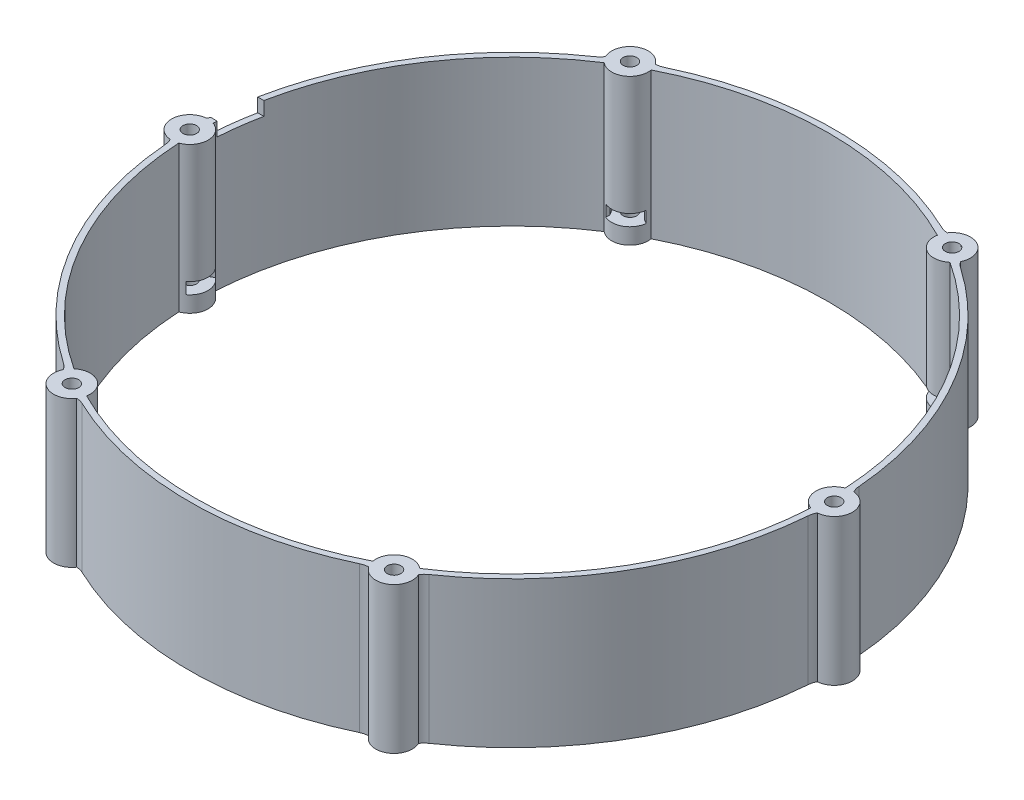
SolidWorks part; units mm, degrees
ref_plane "前视基准面" through (0, 0, 0) normal (0, 0, 1) x (1, 0, 0)
ref_plane "上视基准面" through (0, 0, 0) normal (0, 1, 0) x (1, 0, 0)
ref_plane "右视基准面" through (0, 0, 0) normal (1, 0, 0) x (0, 0, -1)
sketch "草图1" plane through (0, 0, 0) normal (0, 1, 0) x (1, 0, 0)
  line L12 (-35.25, -61.0548) -> (0, 0) construction
  line L13 (-67.3629, 4.3002) -> (-9.579, 4.3002)
  line L14 (-67.3629, -4.3002) -> (-9.579, -4.3002)
  line L15 (9.579, 4.3002) -> (67.3629, 4.3002)
  line L16 (9.579, -4.3002) -> (67.3629, -4.3002)
  line L17 (1.0654, -10.4458) -> (29.9573, -60.4881)
  line L18 (8.5136, -6.1456) -> (37.4056, -56.1878)
  line L19 (-29.9573, 60.4881) -> (-1.0654, 10.4458)
  line L20 (-37.4056, 56.1878) -> (-8.5136, 6.1456)
  line L21 (-8.5136, -6.1456) -> (-37.4056, -56.1878)
  line L22 (-1.0654, -10.4458) -> (-29.9573, -60.4881)
  line L23 (37.4056, 56.1878) -> (8.5136, 6.1456)
  line L24 (29.9573, 60.4881) -> (1.0654, 10.4458)
  line L25 (-9.579, 4.3002) -> (-67.3629, 4.3002)
  line L26 (-9.579, -4.3002) -> (-67.3629, -4.3002)
  line L27 (67.3629, -4.3002) -> (9.579, -4.3002)
  line L28 (67.3629, 4.3002) -> (9.579, 4.3002)
  line L29 (-1.0654, 10.4458) -> (-29.9573, 60.4881)
  line L30 (-8.5136, 6.1456) -> (-37.4056, 56.1878)
  line L31 (29.9573, -60.4881) -> (1.0654, -10.4458)
  line L32 (37.4056, -56.1878) -> (8.5136, -6.1456)
  line L33 (8.5136, 6.1456) -> (37.4056, 56.1878)
  line L34 (1.0654, 10.4458) -> (29.9573, 60.4881)
  line L35 (-37.4056, -56.1878) -> (-8.5136, -6.1456)
  line L36 (-29.9573, -60.4881) -> (-1.0654, -10.4458)
  line L37 (10.5, 0) -> (70.5, 0) construction
  line L38 (-10.5, 0) -> (9.5, 0) construction
  line L47 (-31.5, -54.5596) -> (-6.5, -11.2583) construction
  line L48 (-32.799, -53.8096) -> (-7.799, -10.5083)
  line L49 (-30.201, -55.3096) -> (-5.201, -12.0083)
  line L50 (-63, 0) -> (-13, 0) construction
  line L51 (-63, 1.5) -> (-13, 1.5)
  line L52 (-63, -1.5) -> (-13, -1.5)
  line L53 (-31.5, 54.5596) -> (-6.5, 11.2583) construction
  line L54 (-30.201, 55.3096) -> (-5.201, 12.0083)
  line L55 (-32.799, 53.8096) -> (-7.799, 10.5083)
  line L56 (31.5, 54.5596) -> (6.5, 11.2583) construction
  line L57 (32.799, 53.8096) -> (7.799, 10.5083)
  line L58 (30.201, 55.3096) -> (5.201, 12.0083)
  line L59 (63, 0) -> (13, 0) construction
  line L60 (63, -1.5) -> (13, -1.5)
  line L61 (63, 1.5) -> (13, 1.5)
  line L62 (31.5, -54.5596) -> (6.5, -11.2583) construction
  line L63 (30.201, -55.3096) -> (5.201, -12.0083)
  line L64 (32.799, -53.8096) -> (7.799, -10.5083)
  arc A0 (-7.8594, 1.4934) -> (-7.8594, -1.4934) centre (0, 0) ccw construction
  circle A1 centre (-8, 0) radius 1.5
  circle A2 centre (0, 8) radius 1.5
  circle A3 centre (8, 0) radius 1.5
  circle A4 centre (0, -8) radius 1.5
  arc A5 (-8.5136, 6.1456) -> (-9.579, 4.3002) centre (0, 0) ccw
  arc A6 (-67.3629, -4.3002) -> (-37.4056, -56.1878) centre (0, 0) ccw
  arc A7 (-70.5, 3) -> (-70.5, -3) centre (-70.5, 0) ccw
  circle A8 centre (-70.5, 0) radius 1.5
  arc A9 (-32.6519, 62.5548) -> (-37.8481, 59.5548) centre (-35.25, 61.0548) ccw
  circle A10 centre (-35.25, 61.0548) radius 1.5
  arc A11 (37.8481, 59.5548) -> (32.6519, 62.5548) centre (35.25, 61.0548) ccw
  circle A12 centre (35.25, 61.0548) radius 1.5
  arc A13 (70.5, -3) -> (70.5, 3) centre (70.5, 0) ccw
  circle A14 centre (70.5, 0) radius 1.5
  arc A15 (32.6519, -62.5548) -> (37.8481, -59.5548) centre (35.25, -61.0548) ccw
  circle A16 centre (35.25, -61.0548) radius 1.5
  arc A17 (-37.8481, -59.5548) -> (-32.6519, -62.5548) centre (-35.25, -61.0548) ccw
  circle A18 centre (-35.25, -61.0548) radius 1.5
  arc A21 (1.4934, 7.8594) -> (-6.746, 4.3002) centre (0, 0) ccw construction
  arc A22 (-1.4934, -7.8594) -> (1.4934, -7.8594) centre (0, 0) ccw construction
  arc A23 (7.8594, -1.4934) -> (6.746, 4.3002) centre (0, 0) ccw construction
  circle A24 centre (0, 0) radius 4.5
  arc A25 (1.0654, 10.4458) -> (-1.0654, 10.4458) centre (0, 0) ccw
  arc A26 (9.579, 4.3002) -> (8.5136, 6.1456) centre (0, 0) ccw
  arc A27 (8.5136, -6.1456) -> (9.579, -4.3002) centre (0, 0) ccw
  arc A28 (-1.0654, -10.4458) -> (1.0654, -10.4458) centre (0, 0) ccw
  arc A29 (-9.579, -4.3002) -> (-8.5136, -6.1456) centre (0, 0) ccw
  arc A30 (-37.4056, 56.1878) -> (-67.3629, 4.3002) centre (0, 0) ccw
  arc A31 (29.9573, 60.4881) -> (-29.9573, 60.4881) centre (0, 0) ccw
  arc A32 (67.3629, 4.3002) -> (37.4056, 56.1878) centre (0, 0) ccw
  arc A33 (37.4056, -56.1878) -> (67.3629, -4.3002) centre (0, 0) ccw
  arc A34 (-29.9573, -60.4881) -> (29.9573, -60.4881) centre (0, 0) ccw
  arc A35 (32.6519, 62.5548) -> (-32.6519, 62.5548) centre (0, 0) ccw
  arc A36 (70.5, 3) -> (37.8481, 59.5548) centre (0, 0) ccw
  arc A37 (37.8481, -59.5548) -> (70.5, -3) centre (0, 0) ccw
  arc A38 (-32.6519, -62.5548) -> (32.6519, -62.5548) centre (0, 0) ccw
  arc A39 (-70.5, -3) -> (-37.8481, -59.5548) centre (0, 0) ccw
  arc A40 (-37.8481, 59.5548) -> (-70.5, 3) centre (0, 0) ccw
  arc A41 (-32.799, -53.8096) -> (-30.201, -55.3096) centre (-31.5, -54.5596) ccw
  arc A42 (-5.201, -12.0083) -> (-7.799, -10.5083) centre (-6.5, -11.2583) ccw
  arc A43 (-63, 1.5) -> (-63, -1.5) centre (-63, 0) ccw
  arc A44 (-13, -1.5) -> (-13, 1.5) centre (-13, 0) ccw
  arc A45 (-30.201, 55.3096) -> (-32.799, 53.8096) centre (-31.5, 54.5596) ccw
  arc A46 (-7.799, 10.5083) -> (-5.201, 12.0083) centre (-6.5, 11.2583) ccw
  arc A47 (32.799, 53.8096) -> (30.201, 55.3096) centre (31.5, 54.5596) ccw
  arc A48 (5.201, 12.0083) -> (7.799, 10.5083) centre (6.5, 11.2583) ccw
  arc A49 (63, -1.5) -> (63, 1.5) centre (63, 0) ccw
  arc A50 (13, 1.5) -> (13, -1.5) centre (13, 0) ccw
  arc A51 (30.201, -55.3096) -> (32.799, -53.8096) centre (31.5, -54.5596) ccw
  arc A52 (7.799, -10.5083) -> (5.201, -12.0083) centre (6.5, -11.2583) ccw
  point P14 (0, 0)
  point P15 (0, 0)
  point P20 (-19, -32.909)
  point P51 (-38, 0)
  point P52 (0, 0)
  point P92 (-19, 32.909)
  point P99 (19, 32.909)
  point P106 (38, 0)
  point P111 (0, 0)
  point P130 (19, -32.909)
  point P135 (0, 0)
  dimension "D1" = 16
  dimension "D2" = 3
  dimension "D4" = 2.5
  dimension "D5" = 135
  dimension "D6" = 6
  dimension "D7" = 3
  dimension "D9" = 9
  dimension "D11" = 50
  dimension "D8" = 6
  dimension "D12" = 13
  dimension "D13" = 3
  dimension "D3" = 4
  dimension "D10" = 6
  dimension "D14" = 6
extrude "凸台-拉伸1" add sketch "草图1" along normal blind 4 contours A9 A40 A7 A39 A17 A38 A15 A37 A13 A36 A11 A35 A52 L64 A51 L63 A50 L61 A49 L60 A48 L58 A47 L57 A46 L55 A45 L54 A44 L52 A43 L51 A42 L49 A41 L48 L14 A29 L21 A6 A1 A2 region at (-59.3453, 0, -34.263)
fillet "圆角1" radius 4 24 edges at (-37.4056, 2, 56.1878) (-67.3629, 2, 4.3002) (-70.5, 2, 3) (-70.5, 2, -3) (-67.3629, 2, -4.3002) (-37.4056, 2, -56.1878) (-29.9573, 2, -60.4881) (-37.8481, 2, -59.5548) (-32.6519, 2, -62.5548) (32.6519, 2, -62.5548) (29.9573, 2, -60.4881) (37.4056, 2, -56.1878) (37.8481, 2, -59.5548) (70.5, 2, -3) (70.5, 2, 3) (67.3629, 2, -4.3002) (67.3629, 2, 4.3002) (37.8481, 2, 59.5548) (37.4056, 2, 56.1878) (32.6519, 2, 62.5548) (29.9573, 2, 60.4881) (-37.8481, 2, 59.5548) (-29.9573, 2, 60.4881) (-32.6519, 2, 62.5548)
fillet "圆角2" radius 4 12 edges at (-1.0654, 2, 10.4458) (-8.5136, 2, 6.1456) (-9.579, 2, 4.3002) (-9.579, 2, -4.3002) (-8.5136, 2, -6.1456) (1.0654, 2, -10.4458) (-1.0654, 2, -10.4458) (9.579, 2, -4.3002) (8.5136, 2, -6.1456) (9.579, 2, 4.3002) (8.5136, 2, 6.1456) (1.0654, 2, 10.4458)
sketch "草图2" plane through (0, 0, 0) normal (0, -1, 0) x (-1, 0, 0)
  line L0 (23.0864, -63.4293) -> (23.5994, -64.8388)
  line L1 (0, 0) -> (0, -46.6688) construction
  line L2 (-23.0864, -63.4293) -> (-23.5994, -64.8388)
  line L3 (-43.3882, -51.708) -> (-44.3523, -52.8571)
  line L4 (-66.4745, -11.7213) -> (-67.9517, -11.9817)
  line L5 (-66.4745, 11.7213) -> (-67.9517, 11.9817)
  line L6 (-43.3882, 51.708) -> (-44.3523, 52.8571)
  line L7 (-23.0864, 63.4293) -> (-23.5994, 64.8388)
  line L8 (23.0864, 63.4293) -> (23.5994, 64.8388)
  line L9 (43.3882, 51.708) -> (44.3523, 52.8571)
  line L10 (66.4745, 11.7213) -> (67.9517, 11.9817)
  line L11 (66.4745, -11.7213) -> (67.9517, -11.9817)
  line L12 (43.3882, -51.708) -> (44.3523, -52.8571)
  arc A0 (-23.0864, -63.4293) -> (23.0864, -63.4293) centre (0, 0) ccw
  arc A1 (-23.5994, -64.8388) -> (23.5994, -64.8388) centre (0, 0) ccw
  arc A2 (-66.4745, -11.7213) -> (-43.3882, -51.708) centre (0, 0) ccw
  arc A3 (-67.9517, -11.9817) -> (-44.3523, -52.8571) centre (0, 0) ccw
  arc A4 (-43.3882, 51.708) -> (-66.4745, 11.7213) centre (0, 0) ccw
  arc A5 (-44.3523, 52.8571) -> (-67.9517, 11.9817) centre (0, 0) ccw
  arc A6 (23.0864, 63.4293) -> (-23.0864, 63.4293) centre (0, 0) ccw
  arc A7 (23.5994, 64.8388) -> (-23.5994, 64.8388) centre (0, 0) ccw
  arc A8 (66.4745, 11.7213) -> (43.3882, 51.708) centre (0, 0) ccw
  arc A9 (67.9517, 11.9817) -> (44.3523, 52.8571) centre (0, 0) ccw
  arc A10 (43.3882, -51.708) -> (66.4745, -11.7213) centre (0, 0) ccw
  arc A11 (44.3523, -52.8571) -> (67.9517, -11.9817) centre (0, 0) ccw
  point P30 (0, 0)
  dimension "D1" = 1.5
  dimension "D2" = 20
  dimension "D3" = 6
extrude "凸台-拉伸2" add sketch "草图2" along normal blind 5
chamfer "倒角1" distance 0.5 angle 45 6 edges at (59.7558, -5, -34.5) (59.7558, -5, 34.5) (0, -5, 69) (-59.7558, -5, 34.5) (-59.7558, -5, -34.5) (0, -5, -69)
sketch "草图3" plane through (0, 0, 0) normal (0, -1, 0) x (1, 0, 0)
  arc A0 (-37.8339, 58.0014) -> (-69.1476, 3.7644) centre (0, 0) ccw
  arc A2 (-69.1476, -3.7644) -> (-37.8339, -58.0014) centre (0, 0) ccw
  arc A4 (69.1476, 3.7644) -> (69.1476, -3.7644) centre (70.5, 0) ccw
  arc A5 (69.1476, 3.7644) -> (37.8339, 58.0014) centre (0, 0) ccw
  arc A6 (37.8339, -58.0014) -> (69.1476, -3.7644) centre (0, 0) ccw
  arc A7 (-31.3137, -61.7658) -> (31.3137, -61.7658) centre (0, 0) ccw
  arc A9 (70.7964, -3.989) -> (70.7964, 3.989) centre (70.5, 0) ccw
  arc A10 (31.3137, 61.7658) -> (37.8339, 58.0014) centre (35.25, 61.0548) ccw
  arc A11 (31.3137, 61.7658) -> (-31.3137, 61.7658) centre (0, 0) ccw
  arc A12 (37.8339, -58.0014) -> (31.3137, -61.7658) centre (35.25, -61.0548) ccw
  arc A13 (-38.8528, -59.317) -> (-31.9436, -63.306) centre (-35.25, -61.0548) ccw
  arc A14 (-70.7964, 3.989) -> (-70.7964, -3.989) centre (-70.5, 0) ccw
  arc A15 (-31.9436, 63.306) -> (-38.8528, 59.317) centre (-35.25, 61.0548) ccw
  arc A16 (38.8528, 59.317) -> (31.9436, 63.306) centre (35.25, 61.0548) ccw
  arc A17 (-37.8339, 58.0014) -> (-31.3137, 61.7658) centre (-35.25, 61.0548) ccw
  arc A18 (-69.1476, -3.7644) -> (-69.1476, 3.7644) centre (-70.5, 0) ccw
  arc A19 (-31.3137, -61.7658) -> (-37.8339, -58.0014) centre (-35.25, -61.0548) ccw
  arc A20 (31.9436, -63.306) -> (38.8528, -59.317) centre (35.25, -61.0548) ccw
  circle A21 centre (70.5, 0) radius 1.5
  circle A22 centre (35.25, 61.0548) radius 1.5
  circle A23 centre (-35.25, 61.0548) radius 1.5
  arc A24 (-38.2453, -61.2225) -> (-33.8976, -63.7327) centre (-35.25, -61.0548) ccw
  arc A25 (-30.3726, -63.6926) -> (-33.8976, -63.7327) centre (-32.0944, -67.3031) ccw
  arc A26 (-30.3726, -63.6926) -> (30.3726, -63.6926) centre (0, 0) ccw
  arc A27 (33.8976, -63.7327) -> (30.3726, -63.6926) centre (32.0944, -67.3031) ccw
  arc A28 (33.8976, -63.7327) -> (38.2453, -61.2225) centre (35.25, -61.0548) ccw
  arc A29 (39.9731, -58.1498) -> (38.2453, -61.2225) centre (42.2391, -61.4461) ccw
  arc A30 (39.9731, -58.1498) -> (70.3458, -5.5428) centre (0, 0) ccw
  arc A31 (72.1429, -2.5102) -> (70.3458, -5.5428) centre (74.3334, -5.857) ccw
  arc A32 (72.1429, -2.5102) -> (72.1429, 2.5102) centre (70.5, 0) ccw
  arc A33 (70.3458, 5.5428) -> (72.1429, 2.5102) centre (74.3334, 5.857) ccw
  arc A34 (70.3458, 5.5428) -> (39.9731, 58.1498) centre (0, 0) ccw
  arc A35 (38.2453, 61.2225) -> (39.9731, 58.1498) centre (42.2391, 61.4461) ccw
  arc A36 (38.2453, 61.2225) -> (33.8976, 63.7327) centre (35.25, 61.0548) ccw
  arc A37 (30.3726, 63.6926) -> (33.8976, 63.7327) centre (32.0944, 67.3031) ccw
  arc A38 (30.3726, 63.6926) -> (-30.3726, 63.6926) centre (0, 0) ccw
  arc A39 (-33.8976, 63.7327) -> (-30.3726, 63.6926) centre (-32.0944, 67.3031) ccw
  arc A40 (-33.8976, 63.7327) -> (-38.2453, 61.2225) centre (-35.25, 61.0548) ccw
  arc A41 (-39.9731, 58.1498) -> (-38.2453, 61.2225) centre (-42.2391, 61.4461) ccw
  arc A42 (-39.9731, 58.1498) -> (-70.3458, 5.5428) centre (0, 0) ccw
  arc A43 (-72.1429, 2.5102) -> (-70.3458, 5.5428) centre (-74.3334, 5.857) ccw
  arc A44 (-72.1429, 2.5102) -> (-72.1429, -2.5102) centre (-70.5, 0) ccw
  arc A45 (-70.3458, -5.5428) -> (-72.1429, -2.5102) centre (-74.3334, -5.857) ccw
  arc A46 (-70.3458, -5.5428) -> (-39.9731, -58.1498) centre (0, 0) ccw
  arc A47 (-38.2453, -61.2225) -> (-39.9731, -58.1498) centre (-42.2391, -61.4461) ccw
  arc A49 (-30.3726, -63.6926) -> (-31.9436, -63.306) centre (-32.0944, -67.3031) ccw
  arc A50 (-30.3726, -63.6926) -> (30.3726, -63.6926) centre (0, 0) ccw
  arc A51 (31.9436, -63.306) -> (30.3726, -63.6926) centre (32.0944, -67.3031) ccw
  arc A53 (39.9731, -58.1498) -> (38.8528, -59.317) centre (42.2391, -61.4461) ccw
  arc A54 (39.9731, -58.1498) -> (70.3458, -5.5428) centre (0, 0) ccw
  arc A55 (70.7964, -3.989) -> (70.3458, -5.5428) centre (74.3334, -5.857) ccw
  arc A57 (70.3458, 5.5428) -> (70.7964, 3.989) centre (74.3334, 5.857) ccw
  arc A58 (70.3458, 5.5428) -> (39.9731, 58.1498) centre (0, 0) ccw
  arc A59 (38.8528, 59.317) -> (39.9731, 58.1498) centre (42.2391, 61.4461) ccw
  arc A61 (30.3726, 63.6926) -> (31.9436, 63.306) centre (32.0944, 67.3031) ccw
  arc A62 (30.3726, 63.6926) -> (-30.3726, 63.6926) centre (0, 0) ccw
  arc A63 (-31.9436, 63.306) -> (-30.3726, 63.6926) centre (-32.0944, 67.3031) ccw
  arc A65 (-39.9731, 58.1498) -> (-38.8528, 59.317) centre (-42.2391, 61.4461) ccw
  arc A66 (-39.9731, 58.1498) -> (-70.3458, 5.5428) centre (0, 0) ccw
  arc A67 (-70.7964, 3.989) -> (-70.3458, 5.5428) centre (-74.3334, 5.857) ccw
  arc A69 (-70.3458, -5.5428) -> (-70.7964, -3.989) centre (-74.3334, -5.857) ccw
  arc A70 (-70.3458, -5.5428) -> (-39.9731, -58.1498) centre (0, 0) ccw
  arc A71 (-38.8528, -59.317) -> (-39.9731, -58.1498) centre (-42.2391, -61.4461) ccw
  circle A73 centre (-70.5, 0) radius 1.5
  circle A74 centre (-35.25, -61.0548) radius 1.5
  circle A75 centre (35.25, -61.0548) radius 1.5
  point P57 (0, 0)
  point P80 (0, 0)
  dimension "D2" = 138.5
  dimension "D5" = 8
  dimension "D4" = 6
  dimension "D1" = 0
extrude "凸台-拉伸3" add sketch "草图3" along normal blind 10 from offset 10 separate body
sketch "草图4" plane through (0, 0, 0) normal (0, -1, 0) x (-1, 0, 0)
  line L1 (113.8553, 88.8529) -> (-113.8553, 88.8529)
  line L2 (113.8553, 88.8529) -> (113.8553, -88.8529)
  line L3 (113.8553, -88.8529) -> (-113.8553, -88.8529)
  line L4 (-113.8553, 88.8529) -> (-113.8553, -88.8529)
  line L5 (113.8553, 88.8529) -> (-113.8553, -88.8529) construction
  line L6 (113.8553, -88.8529) -> (-113.8553, 88.8529) construction
  point P0 (0, 0)
extrude "切除-拉伸1" cut sketch "草图4" against normal blind 10 and the other way blind 7
sketch "草图5" plane through (0, -10, 0) normal (0, 1, 0) x (1, 0, 0)
  line L2 (-32.0168, 61.0548) -> (-33.6334, 63.8548)
  line L3 (-33.6334, 63.8548) -> (-36.8666, 63.8548)
  line L4 (-36.8666, 63.8548) -> (-38.4832, 61.0548)
  line L5 (-38.4832, 61.0548) -> (-36.8666, 58.2548)
  line L7 (36.8666, 58.2548) -> (38.4832, 61.0548)
  line L8 (38.4832, 61.0548) -> (36.8666, 63.8548)
  line L9 (36.8666, 63.8548) -> (33.6334, 63.8548)
  line L10 (33.6334, 63.8548) -> (32.0168, 61.0548)
  line L13 (68.8834, -2.8) -> (72.1166, -2.8)
  line L14 (72.1166, -2.8) -> (73.7332, 0)
  line L15 (73.7332, 0) -> (72.1166, 2.8)
  line L16 (72.1166, 2.8) -> (68.8834, 2.8)
  line L19 (32.0168, -61.0548) -> (33.6334, -63.8548)
  line L20 (33.6334, -63.8548) -> (36.8666, -63.8548)
  line L21 (36.8666, -63.8548) -> (38.4832, -61.0548)
  line L22 (38.4832, -61.0548) -> (36.8666, -58.2548)
  line L25 (-36.8666, -58.2548) -> (-38.4832, -61.0548)
  line L26 (-38.4832, -61.0548) -> (-36.8666, -63.8548)
  line L27 (-36.8666, -63.8548) -> (-33.6334, -63.8548)
  line L28 (-33.6334, -63.8548) -> (-32.0168, -61.0548)
  line L31 (-68.8834, 2.8) -> (-72.1166, 2.8)
  line L32 (-72.1166, 2.8) -> (-73.7332, 0)
  line L33 (-73.7332, 0) -> (-72.1166, -2.8)
  line L34 (-72.1166, -2.8) -> (-68.8834, -2.8)
  line L36 (-36.8666, 58.2548) -> (-36.8666, 57.396)
  line L37 (32.0168, 61.0548) -> (31.2731, 60.6254)
  line L38 (-32.0168, 61.0548) -> (-31.2731, 60.6254)
  line L39 (-32.8251, 59.6548) -> (-32.0168, 61.0548) [skipped]
  line L40 (-36.8666, 58.2548) -> (-35.25, 58.2548) [skipped]
  line L41 (36.8666, 58.2548) -> (36.8666, 57.396)
  line L42 (68.8834, 2.8) -> (68.1397, 3.2294)
  line L43 (68.8834, -2.8) -> (68.1397, -3.2294)
  line L44 (36.8666, -58.2548) -> (36.8666, -57.396)
  line L45 (32.0168, -61.0548) -> (31.2731, -60.6254)
  line L46 (-32.0168, -61.0548) -> (-31.2731, -60.6254)
  line L47 (-36.8666, -58.2548) -> (-36.8666, -57.396)
  line L48 (-68.8834, -2.8) -> (-68.1397, -3.2294)
  line L49 (-68.8834, 2.8) -> (-68.1397, 3.2294)
  arc A0 (-32.8251, 62.4548) -> (-37.6749, 59.6548) centre (-35.25, 61.0548) ccw construction
  arc A1 (-37.8339, 58.0014) -> (-31.3137, 61.7658) centre (-35.25, 61.0548) ccw construction
  arc A2 (-37.8339, 58.0014) -> (-69.1476, 3.7644) centre (0, 0) ccw construction
  arc A3 (-69.1476, -3.7644) -> (-69.1476, 3.7644) centre (-70.5, 0) ccw construction
  arc A4 (-69.1476, -3.7644) -> (-37.8339, -58.0014) centre (0, 0) ccw construction
  arc A5 (-31.3137, -61.7658) -> (-37.8339, -58.0014) centre (-35.25, -61.0548) ccw construction
  arc A6 (-31.3137, -61.7658) -> (31.3137, -61.7658) centre (0, 0) ccw construction
  arc A7 (37.8339, -58.0014) -> (31.3137, -61.7658) centre (35.25, -61.0548) ccw construction
  arc A8 (37.8339, -58.0014) -> (69.1476, -3.7644) centre (0, 0) ccw construction
  arc A9 (69.1476, 3.7644) -> (69.1476, -3.7644) centre (70.5, 0) ccw construction
  arc A10 (69.1476, 3.7644) -> (37.8339, 58.0014) centre (0, 0) ccw construction
  arc A11 (31.3137, 61.7658) -> (37.8339, 58.0014) centre (35.25, 61.0548) ccw construction
  arc A12 (31.3137, 61.7658) -> (-31.3137, 61.7658) centre (0, 0) ccw construction
  arc A13 (-37.8339, 58.0014) -> (-36.8666, 57.396) centre (-35.25, 61.0548) ccw
  arc A14 (-37.8339, 58.0014) -> (-69.1476, 3.7644) centre (0, 0) ccw
  arc A15 (-69.1476, -3.7644) -> (-68.1397, -3.2294) centre (-70.5, 0) ccw
  arc A16 (-69.1476, -3.7644) -> (-37.8339, -58.0014) centre (0, 0) ccw
  arc A17 (-31.3137, -61.7658) -> (-31.2731, -60.6254) centre (-35.25, -61.0548) ccw
  arc A18 (-31.3137, -61.7658) -> (31.3137, -61.7658) centre (0, 0) ccw
  arc A19 (37.8339, -58.0014) -> (36.8666, -57.396) centre (35.25, -61.0548) ccw
  arc A20 (37.8339, -58.0014) -> (69.1476, -3.7644) centre (0, 0) ccw
  arc A21 (69.1476, 3.7644) -> (68.1397, 3.2294) centre (70.5, 0) ccw
  arc A22 (69.1476, 3.7644) -> (37.8339, 58.0014) centre (0, 0) ccw
  arc A23 (31.3137, 61.7658) -> (31.2731, 60.6254) centre (35.25, 61.0548) ccw
  arc A24 (31.3137, 61.7658) -> (-31.3137, 61.7658) centre (0, 0) ccw
  arc A25 (30.3726, 63.6926) -> (-30.3726, 63.6926) centre (0, 0) ccw
  arc A26 (-31.9436, 63.306) -> (-30.3726, 63.6926) centre (-32.0944, 67.3031) ccw
  arc A27 (-31.9436, 63.306) -> (-38.8528, 59.317) centre (-35.25, 61.0548) ccw
  arc A28 (-39.9731, 58.1498) -> (-38.8528, 59.317) centre (-42.2391, 61.4461) ccw
  arc A29 (-39.9731, 58.1498) -> (-70.3458, 5.5428) centre (0, 0) ccw
  arc A30 (-70.7964, 3.989) -> (-70.3458, 5.5428) centre (-74.3334, 5.857) ccw
  arc A31 (-70.7964, 3.989) -> (-70.7964, -3.989) centre (-70.5, 0) ccw
  arc A32 (-70.3458, -5.5428) -> (-70.7964, -3.989) centre (-74.3334, -5.857) ccw
  arc A33 (-70.3458, -5.5428) -> (-39.9731, -58.1498) centre (0, 0) ccw
  arc A34 (-38.8528, -59.317) -> (-39.9731, -58.1498) centre (-42.2391, -61.4461) ccw
  arc A35 (-38.8528, -59.317) -> (-31.9436, -63.306) centre (-35.25, -61.0548) ccw
  arc A36 (-30.3726, -63.6926) -> (-31.9436, -63.306) centre (-32.0944, -67.3031) ccw
  arc A37 (-30.3726, -63.6926) -> (30.3726, -63.6926) centre (0, 0) ccw
  arc A38 (31.9436, -63.306) -> (30.3726, -63.6926) centre (32.0944, -67.3031) ccw
  arc A39 (31.9436, -63.306) -> (38.8528, -59.317) centre (35.25, -61.0548) ccw
  arc A40 (39.9731, -58.1498) -> (38.8528, -59.317) centre (42.2391, -61.4461) ccw
  arc A41 (39.9731, -58.1498) -> (70.3458, -5.5428) centre (0, 0) ccw
  arc A42 (70.7964, -3.989) -> (70.3458, -5.5428) centre (74.3334, -5.857) ccw
  arc A43 (70.7964, -3.989) -> (70.7964, 3.989) centre (70.5, 0) ccw
  arc A44 (70.3458, 5.5428) -> (70.7964, 3.989) centre (74.3334, 5.857) ccw
  arc A45 (70.3458, 5.5428) -> (39.9731, 58.1498) centre (0, 0) ccw
  arc A46 (38.8528, 59.317) -> (39.9731, 58.1498) centre (42.2391, 61.4461) ccw
  arc A47 (38.8528, 59.317) -> (31.9436, 63.306) centre (35.25, 61.0548) ccw
  arc A48 (30.3726, 63.6926) -> (31.9436, 63.306) centre (32.0944, 67.3031) ccw
  arc A49 (30.3726, 63.6926) -> (-30.3726, 63.6926) centre (0, 0) ccw
  arc A50 (-31.9436, 63.306) -> (-30.3726, 63.6926) centre (-32.0944, 67.3031) ccw
  arc A51 (-31.9436, 63.306) -> (-38.8528, 59.317) centre (-35.25, 61.0548) ccw
  arc A52 (-39.9731, 58.1498) -> (-38.8528, 59.317) centre (-42.2391, 61.4461) ccw
  arc A53 (-39.9731, 58.1498) -> (-70.3458, 5.5428) centre (0, 0) ccw
  arc A54 (-70.7964, 3.989) -> (-70.3458, 5.5428) centre (-74.3334, 5.857) ccw
  arc A55 (-70.7964, 3.989) -> (-70.7964, -3.989) centre (-70.5, 0) ccw
  arc A56 (-70.3458, -5.5428) -> (-70.7964, -3.989) centre (-74.3334, -5.857) ccw
  arc A57 (-70.3458, -5.5428) -> (-39.9731, -58.1498) centre (0, 0) ccw
  arc A58 (-38.8528, -59.317) -> (-39.9731, -58.1498) centre (-42.2391, -61.4461) ccw
  arc A59 (-38.8528, -59.317) -> (-31.9436, -63.306) centre (-35.25, -61.0548) ccw
  arc A60 (-30.3726, -63.6926) -> (-31.9436, -63.306) centre (-32.0944, -67.3031) ccw
  arc A61 (-30.3726, -63.6926) -> (30.3726, -63.6926) centre (0, 0) ccw
  arc A62 (31.9436, -63.306) -> (30.3726, -63.6926) centre (32.0944, -67.3031) ccw
  arc A63 (31.9436, -63.306) -> (38.8528, -59.317) centre (35.25, -61.0548) ccw
  arc A64 (39.9731, -58.1498) -> (38.8528, -59.317) centre (42.2391, -61.4461) ccw
  arc A65 (39.9731, -58.1498) -> (70.3458, -5.5428) centre (0, 0) ccw
  arc A66 (70.7964, -3.989) -> (70.3458, -5.5428) centre (74.3334, -5.857) ccw
  arc A67 (70.7964, -3.989) -> (70.7964, 3.989) centre (70.5, 0) ccw
  arc A68 (70.3458, 5.5428) -> (70.7964, 3.989) centre (74.3334, 5.857) ccw
  arc A69 (70.3458, 5.5428) -> (39.9731, 58.1498) centre (0, 0) ccw
  arc A70 (38.8528, 59.317) -> (39.9731, 58.1498) centre (42.2391, 61.4461) ccw
  arc A71 (38.8528, 59.317) -> (31.9436, 63.306) centre (35.25, 61.0548) ccw
  arc A72 (30.3726, 63.6926) -> (31.9436, 63.306) centre (32.0944, 67.3031) ccw
  arc A73 (-31.2731, 60.6254) -> (-31.3137, 61.7658) centre (-35.25, 61.0548) ccw
  arc A74 (36.8666, 57.396) -> (37.8339, 58.0014) centre (35.25, 61.0548) ccw
  arc A75 (68.1397, -3.2294) -> (69.1476, -3.7644) centre (70.5, 0) ccw
  arc A76 (31.2731, -60.6254) -> (31.3137, -61.7658) centre (35.25, -61.0548) ccw
  arc A77 (-36.8666, -57.396) -> (-37.8339, -58.0014) centre (-35.25, -61.0548) ccw
  arc A78 (-68.1397, 3.2294) -> (-69.1476, 3.7644) centre (-70.5, 0) ccw
  point P42 (0, 0)
  point P141 (0, 0)
  dimension "D1" = 5.6
  dimension "D4" = 6
  dimension "D3" = 0
  dimension "D2" = 6
extrude "凸台-拉伸4" add sketch "草图5" along normal blind 2.5
sketch "草图7" plane through (0, -20, 0) normal (0, -1, 0) x (-1, 0, 0)
  circle A0 centre (0, 0) radius 85.197
extrude "切除-拉伸2" cut sketch "草图7" against normal blind 6.5
sketch "草图8" plane through (0, -7.5, 0) normal (0, 1, 0) x (1, 0, 0)
  circle A0 centre (-35.25, 61.0548) radius 1.5
  arc A1 (-37.8339, 58.0014) -> (-31.3137, 61.7658) centre (-35.25, 61.0548) ccw
  arc A2 (-31.9436, 63.306) -> (-38.8528, 59.317) centre (-35.25, 61.0548) ccw construction
  arc A3 (-31.9436, 63.306) -> (-38.8528, 59.317) centre (-35.25, 61.0548) ccw
  arc A4 (31.3137, 61.7658) -> (-31.3137, 61.7658) centre (0, 0) ccw construction
  arc A5 (-37.8339, 58.0014) -> (-69.1476, 3.7644) centre (0, 0) ccw construction
  arc A6 (31.3137, 61.7658) -> (-31.3137, 61.7658) centre (0, 0) ccw
  arc A7 (-37.8339, 58.0014) -> (-69.1476, 3.7644) centre (0, 0) ccw
  circle A8 centre (35.25, 61.0548) radius 1.5
  arc A9 (31.3137, 61.7658) -> (37.8339, 58.0014) centre (35.25, 61.0548) ccw
  arc A10 (69.1476, 3.7644) -> (37.8339, 58.0014) centre (0, 0) ccw
  arc A11 (31.3137, 61.7658) -> (-31.3137, 61.7658) centre (0, 0) ccw
  circle A12 centre (70.5, 0) radius 1.5
  arc A13 (69.1476, 3.7644) -> (69.1476, -3.7644) centre (70.5, 0) ccw
  arc A14 (37.8339, -58.0014) -> (69.1476, -3.7644) centre (0, 0) ccw
  arc A15 (69.1476, 3.7644) -> (37.8339, 58.0014) centre (0, 0) ccw
  circle A16 centre (35.25, -61.0548) radius 1.5
  arc A17 (37.8339, -58.0014) -> (31.3137, -61.7658) centre (35.25, -61.0548) ccw
  arc A18 (-31.3137, -61.7658) -> (31.3137, -61.7658) centre (0, 0) ccw
  arc A19 (37.8339, -58.0014) -> (69.1476, -3.7644) centre (0, 0) ccw
  circle A20 centre (-35.25, -61.0548) radius 1.5
  arc A21 (-31.3137, -61.7658) -> (-37.8339, -58.0014) centre (-35.25, -61.0548) ccw
  arc A22 (-69.1476, -3.7644) -> (-37.8339, -58.0014) centre (0, 0) ccw
  arc A23 (-31.3137, -61.7658) -> (31.3137, -61.7658) centre (0, 0) ccw
  arc A24 (30.3726, 63.6926) -> (31.9436, 63.306) centre (32.0944, 67.3031) ccw
  arc A25 (30.3726, 63.6926) -> (-30.3726, 63.6926) centre (0, 0) ccw
  arc A26 (-31.9436, 63.306) -> (-30.3726, 63.6926) centre (-32.0944, 67.3031) ccw
  arc A27 (-31.9436, 63.306) -> (-38.8528, 59.317) centre (-35.25, 61.0548) ccw
  arc A28 (-39.9731, 58.1498) -> (-38.8528, 59.317) centre (-42.2391, 61.4461) ccw
  arc A29 (-39.9731, 58.1498) -> (-70.3458, 5.5428) centre (0, 0) ccw
  arc A30 (-70.7964, 3.989) -> (-70.3458, 5.5428) centre (-74.3334, 5.857) ccw
  arc A31 (-70.7964, 3.989) -> (-70.7964, -3.989) centre (-70.5, 0) ccw
  arc A32 (-70.3458, -5.5428) -> (-70.7964, -3.989) centre (-74.3334, -5.857) ccw
  arc A33 (-70.3458, -5.5428) -> (-39.9731, -58.1498) centre (0, 0) ccw
  arc A34 (-38.8528, -59.317) -> (-39.9731, -58.1498) centre (-42.2391, -61.4461) ccw
  arc A35 (-38.8528, -59.317) -> (-31.9436, -63.306) centre (-35.25, -61.0548) ccw
  arc A36 (-30.3726, -63.6926) -> (-31.9436, -63.306) centre (-32.0944, -67.3031) ccw
  arc A37 (-30.3726, -63.6926) -> (30.3726, -63.6926) centre (0, 0) ccw
  arc A38 (31.9436, -63.306) -> (30.3726, -63.6926) centre (32.0944, -67.3031) ccw
  arc A39 (31.9436, -63.306) -> (38.8528, -59.317) centre (35.25, -61.0548) ccw
  arc A40 (39.9731, -58.1498) -> (38.8528, -59.317) centre (42.2391, -61.4461) ccw
  arc A41 (39.9731, -58.1498) -> (70.3458, -5.5428) centre (0, 0) ccw
  arc A42 (70.7964, -3.989) -> (70.3458, -5.5428) centre (74.3334, -5.857) ccw
  arc A43 (70.7964, -3.989) -> (70.7964, 3.989) centre (70.5, 0) ccw
  arc A44 (70.3458, 5.5428) -> (70.7964, 3.989) centre (74.3334, 5.857) ccw
  arc A45 (70.3458, 5.5428) -> (39.9731, 58.1498) centre (0, 0) ccw
  arc A46 (38.8528, 59.317) -> (39.9731, 58.1498) centre (42.2391, 61.4461) ccw
  arc A47 (38.8528, 59.317) -> (31.9436, 63.306) centre (35.25, 61.0548) ccw
  arc A48 (30.3726, 63.6926) -> (31.9436, 63.306) centre (32.0944, 67.3031) ccw
  arc A49 (30.3726, 63.6926) -> (-30.3726, 63.6926) centre (0, 0) ccw
  arc A50 (-31.9436, 63.306) -> (-30.3726, 63.6926) centre (-32.0944, 67.3031) ccw
  arc A52 (-39.9731, 58.1498) -> (-38.8528, 59.317) centre (-42.2391, 61.4461) ccw
  arc A53 (-39.9731, 58.1498) -> (-70.3458, 5.5428) centre (0, 0) ccw
  arc A54 (-70.7964, 3.989) -> (-70.3458, 5.5428) centre (-74.3334, 5.857) ccw
  arc A55 (-70.7964, 3.989) -> (-70.7964, -3.989) centre (-70.5, 0) ccw
  arc A56 (-70.3458, -5.5428) -> (-70.7964, -3.989) centre (-74.3334, -5.857) ccw
  arc A57 (-70.3458, -5.5428) -> (-39.9731, -58.1498) centre (0, 0) ccw
  arc A58 (-38.8528, -59.317) -> (-39.9731, -58.1498) centre (-42.2391, -61.4461) ccw
  arc A59 (-38.8528, -59.317) -> (-31.9436, -63.306) centre (-35.25, -61.0548) ccw
  arc A60 (-30.3726, -63.6926) -> (-31.9436, -63.306) centre (-32.0944, -67.3031) ccw
  arc A61 (-30.3726, -63.6926) -> (30.3726, -63.6926) centre (0, 0) ccw
  arc A62 (31.9436, -63.306) -> (30.3726, -63.6926) centre (32.0944, -67.3031) ccw
  arc A63 (31.9436, -63.306) -> (38.8528, -59.317) centre (35.25, -61.0548) ccw
  arc A64 (39.9731, -58.1498) -> (38.8528, -59.317) centre (42.2391, -61.4461) ccw
  arc A65 (39.9731, -58.1498) -> (70.3458, -5.5428) centre (0, 0) ccw
  arc A66 (70.7964, -3.989) -> (70.3458, -5.5428) centre (74.3334, -5.857) ccw
  arc A67 (70.7964, -3.989) -> (70.7964, 3.989) centre (70.5, 0) ccw
  arc A68 (70.3458, 5.5428) -> (70.7964, 3.989) centre (74.3334, 5.857) ccw
  arc A69 (70.3458, 5.5428) -> (39.9731, 58.1498) centre (0, 0) ccw
  arc A70 (38.8528, 59.317) -> (39.9731, 58.1498) centre (42.2391, 61.4461) ccw
  arc A71 (38.8528, 59.317) -> (31.9436, 63.306) centre (35.25, 61.0548) ccw
  circle A72 centre (-70.5, 0) radius 1.5
  arc A73 (-69.1476, -3.7644) -> (-69.1476, 3.7644) centre (-70.5, 0) ccw
  arc A74 (-37.8339, 58.0014) -> (-69.1476, 3.7644) centre (0, 0) ccw
  arc A75 (-69.1476, -3.7644) -> (-37.8339, -58.0014) centre (0, 0) ccw
  point P89 (0, 0)
  dimension "D2" = 6
  dimension "D1" = 0
extrude "凸台-拉伸5" add sketch "草图8" along normal blind 26 contours A70 A71 A48 A49 A50 A3 A52 A53 A54 A55 A56 A57 A58 A59 A60 A61 A62 A63 A64 A65 A66 A67 A68 A69 A72 A0 A8 A12 A16 A20 A22 A73 A7 A1 A6 A9 A10 A13 A14 A17 A18 A21 region at (-31.0893, -7.5, -63.2198)
sketch "草图14" plane through (0, 18.5, 0) normal (0, 1, 0) x (1, 0, 0)
  line L1 (-78.7421, 13.597) -> (-64.6975, 13.597)
  line L2 (-78.7421, 13.597) -> (-78.7421, 4.597)
  line L3 (-78.7421, 4.597) -> (-64.6975, 4.597)
  line L4 (-64.6975, 13.597) -> (-64.6975, 4.597)
  line L5 (-78.7421, 13.597) -> (-64.6975, 4.597) construction
  line L6 (-78.7421, 4.597) -> (-64.6975, 13.597) construction
  point P0 (-71.7198, 9.097)
  dimension "D1" = 9
extrude "切除-拉伸4" cut sketch "草图14" against normal blind 3
